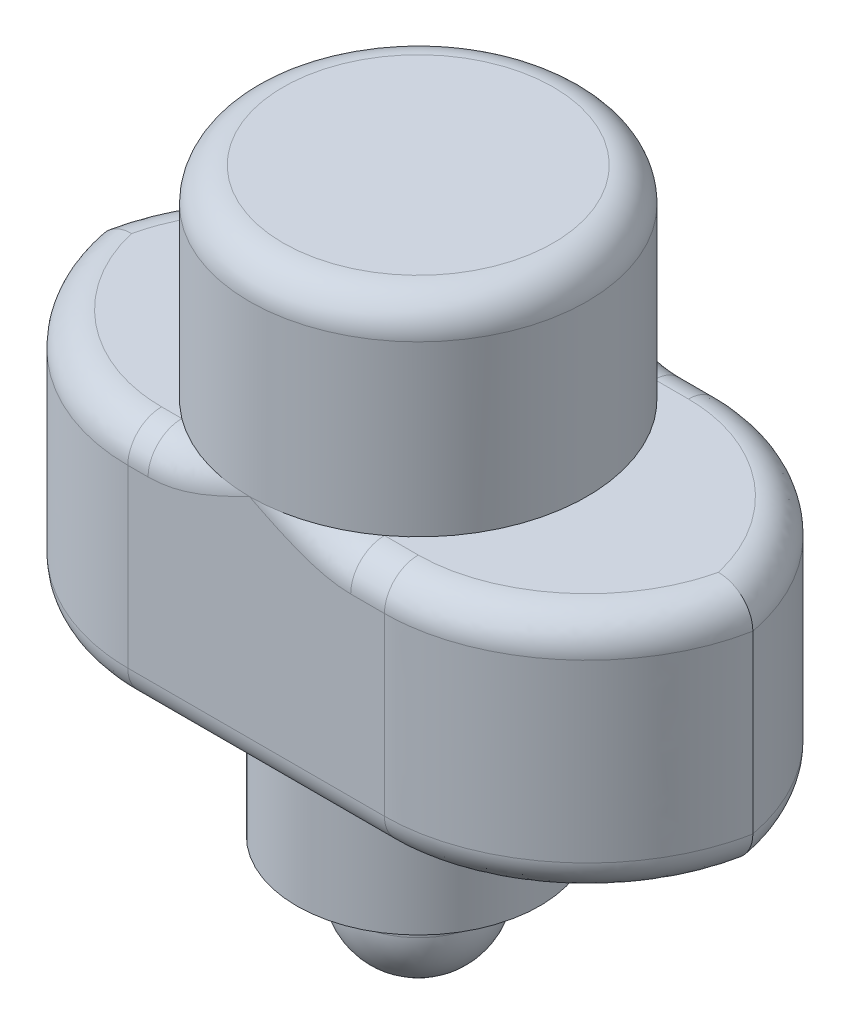
SolidWorks part; units mm, degrees
ref_plane "Front Plane" through (0, 0, 0) normal (0, 0, 1) x (1, 0, 0)
ref_plane "Top Plane" through (0, 0, 0) normal (0, 1, 0) x (1, 0, 0)
ref_plane "Right Plane" through (0, 0, 0) normal (1, 0, 0) x (0, 0, -1)
sketch "Sketch1" plane through (0, 0, 0) normal (0, 1, 0) x (1, 0, 0)
  circle A0 centre (0, 0) radius 1
  dimension "D1" = 2
extrude "Boss-Extrude1" add sketch "Sketch1" along normal blind 1.6 contours A0
fillet "Fillet1" radius 1 1 edges at (0, 0, 1)
ref_plane "Plane1" through (0, 1.6, 0) normal (0, 1, 0) x (1, 0, 0)
sketch "Sketch2" plane through (0, 1.6, 0) normal (0, 1, 0) x (1, 0, 0)
  circle A0 centre (0, 0) radius 1.8
  dimension "D1" = 3.6
extrude "Boss-Extrude2" add sketch "Sketch2" along normal blind 2
ref_plane "Plane2" through (0, 3.6, 0) normal (0, 1, 0) x (1, 0, 0)
sketch "Sketch4" plane through (0, 3.6, 0) normal (0, 1, 0) x (1, 0, 0)
  line L1 (-4.8, 2.5) -> (5, 2.5)
  line L2 (-4.8, 2.5) -> (-4.8, -2.5)
  line L3 (-4.8, -2.5) -> (5, -2.5)
  line L4 (5, 2.5) -> (5, -2.5)
  dimension "D1" = 9.8
  dimension "D2" = 5
  dimension "D3" = 5
  dimension "D4" = 2.5
extrude "Boss-Extrude3" add sketch "Sketch4" along normal blind 3.6
fillet "Fillet2" radius 3 4 edges at (5, 5.4, 2.5) (5, 5.4, -2.5) (-4.8, 5.4, -2.5) (-4.8, 5.4, 2.5) conic rho 0.4
ref_plane "Plane3" through (0, 7.2, 0) normal (0, 1, 0) x (1, 0, 0)
sketch "Sketch5" plane through (0, 7.2, 0) normal (0, 1, 0) x (1, 0, 0)
  circle A0 centre (0, 0) radius 2.5
extrude "Boss-Extrude4" add sketch "Sketch5" along normal blind 3
fillet "Fillet4" radius 0.5 15 edges at (0, 10.2, 2.5)
